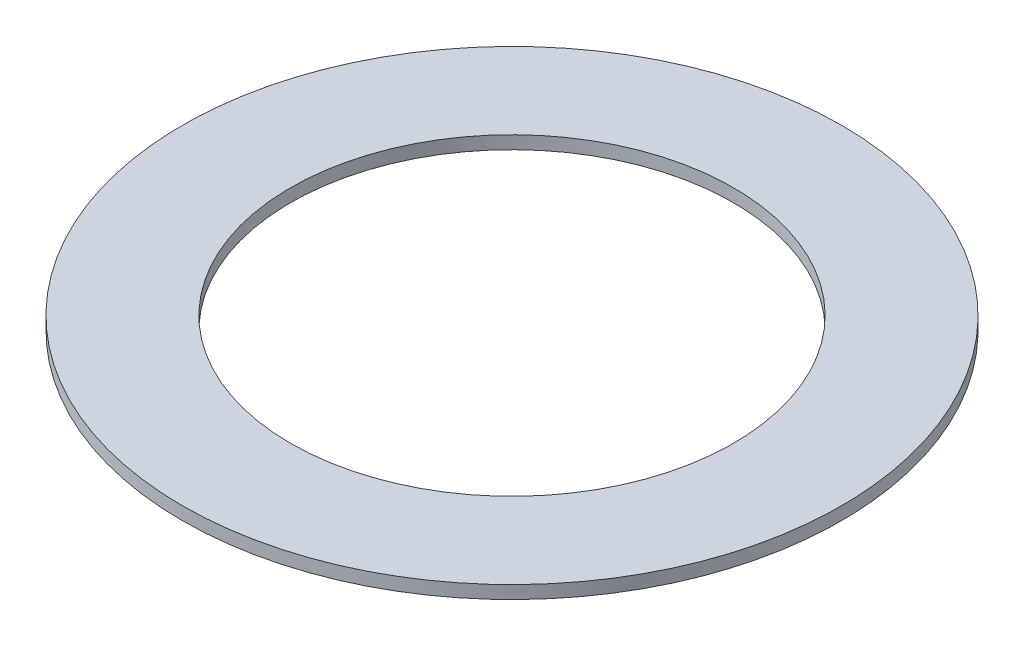
SolidWorks part; units mm, degrees
material "1060 Alloy"
ref_plane "Front Plane" through (0, 0, 0) normal (0, 0, 1) x (1, 0, 0)
ref_plane "Top Plane" through (0, 0, 0) normal (0, 1, 0) x (1, 0, 0)
ref_plane "Right Plane" through (0, 0, 0) normal (1, 0, 0) x (0, 0, -1)
sketch "Sketch1" plane through (0, 0, 0) normal (0, 1, 0) x (1, 0, 0)
  circle A0 centre (0, 0) radius 76.2
  circle A1 centre (0, 0) radius 51.2
  circle A2 centre (0, 0) radius 76.2 construction
  dimension "D1" = 152.4
  dimension "D2" = 102.4
  dimension "D3" = 152.4
extrude "Boss-Extrude1" add sketch "Sketch1" along normal blind 1.5 and the other way blind 1.5
